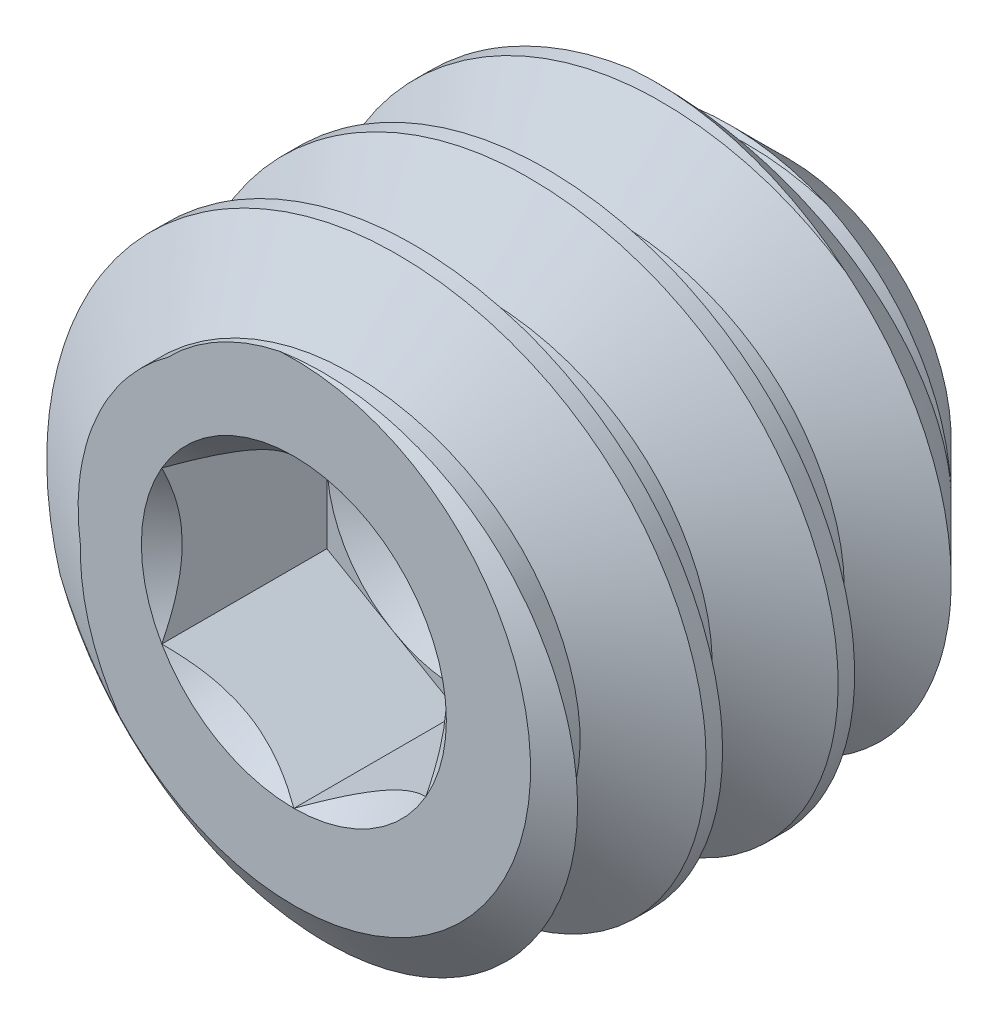
SolidWorks part; units mm, degrees
material "AISI 304"
ref_plane "Front" through (0, 0, 0) normal (0, 0, 1) x (1, 0, 0)
ref_plane "Top" through (0, 0, 0) normal (0, 1, 0) x (1, 0, 0)
ref_plane "Right" through (0, 0, 0) normal (1, 0, 0) x (0, 0, -1)
sketch "Sketch22" plane through (0, 0, 0) normal (1, 0, 0) x (0, 0, -1)
  line L0 (-0.9565, 0) -> (-0.9565, 1.1379)
  line L1 (-0.9565, 1.1379) -> (-0.7573, 1.4224)
  line L2 (-0.7573, 1.4224) -> (0.7818, 1.4224)
  line L3 (0.7818, 1.4224) -> (1.4248, 0.7794)
  line L4 (1.4248, 0.7794) -> (0.9565, 0)
  line L5 (0.9565, 0) -> (-0.9565, 0)
  line L6 (0.9565, 0) -> (1.4248, 0) construction
  line L7 (1.4248, 0) -> (1.4248, 0.7794) construction
  line L8 (1.4248, -0.7794) -> (0.9565, 0) construction
  line L9 (-0.7573, -1.4224) -> (0.7818, -1.4224) construction
  dimension "Dia" = 2.8448
  dimension "Length" = 2.3813
  dimension "D3" = 35
  dimension "D5" = 118
  dimension "D6" = 45
  dimension "D7" = 2.2758
revolve "Revolve1" add sketch "Sketch22" angle 360 about L6
ref_plane "Plane1" through (0, 0, -1.4248) normal (0, 0, 1) x (1, 0, 0)
sketch "Sketch27" plane through (0, 0, -1.4248) normal (0, 0, 1) x (1, 0, 0)
  circle A0 centre (0, 0) radius 1.4224 construction
  circle A1 centre (0, 0) radius 1.4224
curve "Helix/Spiral1" pitch 0.635 height 3.2703 radius 1.4224 centre (0, 0, -1.4248) axis (0, 0, 1) start towards (0, 1, 0)
sketch "Sketch28" plane through (0, 0, 0) normal (1, 0, 0) x (0, 0, -1)
  line L0 (1.4248, 1.4224) -> (1.9804, 1.4224)
  line L1 (1.9804, 1.4224) -> (1.7582, 1.0375)
  line L2 (1.7582, 1.0375) -> (1.647, 1.0375)
  line L3 (1.647, 1.0375) -> (1.4248, 1.4224)
  line L4 (1.5359, 1.2299) -> (1.8693, 1.2299) construction
  line L6 (-0.7573, 1.4224) -> (0.7818, 1.4224) construction
  line L7 (1.4248, 1.6137) -> (1.4248, -1.6137) construction
  dimension "D1" = 0.1111
  dimension "D3" = 60
  dimension "D2" = 0.5556
sweep "Cut-Sweep2" cut profiles "Sketch28" path "Helix/Spiral1" align with end faces yes
sketch "Sketch23" plane through (0, 0, 0.9565) normal (0, 0, 1) x (1, 0, 0)
  line L1 (0, 0.7332) -> (-0.635, 0.3666)
  line L2 (-0.635, 0.3666) -> (-0.635, -0.3666)
  line L3 (-0.635, -0.3666) -> (0, -0.7332)
  line L4 (0, -0.7332) -> (0.635, -0.3666)
  line L5 (0.635, -0.3666) -> (0.635, 0.3666)
  line L6 (0.635, 0.3666) -> (0, 0.7332)
  circle A0 centre (0, 0) radius 0.635 construction
  dimension "Hex" = 1.27
extrude "Cut-Extrude10" cut sketch "Sketch23" against normal blind 0.7937
sketch "Sketch24" plane through (0, 0, 0.9565) normal (0, 0, 1) x (1, 0, 0)
  circle A0 centre (0, 0) radius 0.7332
extrude "Cut-Extrude11" cut sketch "Sketch24" against normal through all draft 45
sketch "Sketch26" plane through (0, 0, 0.1627) normal (0, 0, 1) x (1, 0, 0)
  circle A0 centre (0, 0) radius 0.635 construction
  circle A1 centre (0, 0) radius 0.635
extrude "Cut-Extrude12" cut sketch "Sketch26" against normal through all draft 60
sketch "Sketch30" plane through (0, 0, 0) normal (1, 0, 0) x (0, 0, -1)
  line L0 (-0.7573, 1.4224) -> (0.7818, 1.4224) construction
  line L1 (-0.9565, 0) -> (-0.9565, 1.1379) construction
  line L2 (1.4248, 0) -> (1.4248, 0.7794) construction
  line L3 (-0.7573, -1.4224) -> (0.7818, -1.4224) construction
  point P0 (-0.9565, 1.4224)
  point P1 (1.4248, 1.4224)
  point P2 (1.4248, -1.4224)
  point P11 (-0.1627, -1.4224)
  dimension "D1" = 1.5875
sketch "Sketch31" plane through (0, 0, 0) normal (1, 0, 0) x (0, 0, -1)
  line L2 (0.9565, 0) -> (1.4248, -0.7794)
  line L3 (1.4248, 0.7794) -> (0.9565, 0)
equation "\"D7@Sketch22\"=\"Dia@Sketch22\"*.8"
equation "\"D1@Sketch28\" = \"D4@Helix/Spiral1\" * .175"
equation "\"D3@Helix/Spiral1\" = \"Length@Sketch22\" + \"D4@Helix/Spiral1\" + .01"
equation "\"D1@Sketch30\" = \"D4@Helix/Spiral1\" * 2.5"
equation "\"hex Depth@Cut-Extrude10\" = \"Hex@Sketch23\" * .625"
equation "\"D2@Sketch28\" = \"D4@Helix/Spiral1\" * .875"
